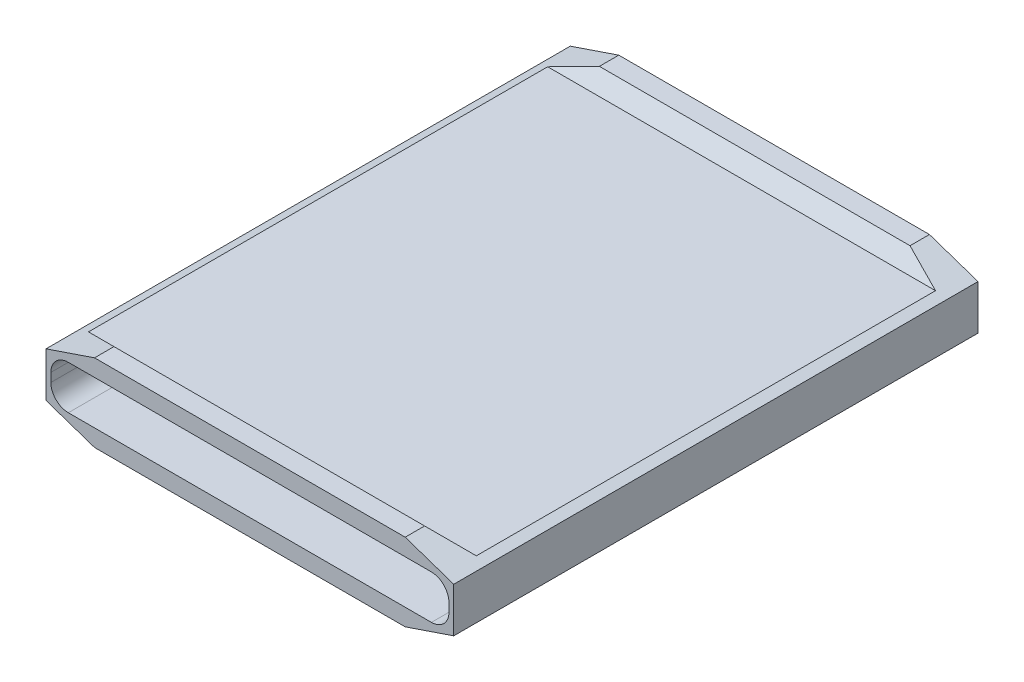
SolidWorks part; units mm, degrees
ref_plane "Front Plane" through (0, 0, 0) normal (0, 0, 1) x (1, 0, 0)
ref_plane "Top Plane" through (0, 0, 0) normal (0, 1, 0) x (1, 0, 0)
ref_plane "Right Plane" through (0, 0, 0) normal (1, 0, 0) x (0, 0, -1)
sketch "Sketch1" plane through (0, 0, 0) normal (0, 0, 1) x (1, 0, 0)
  line L0 (-21, 4) -> (21, 4)
  line L1 (-21, 4) -> (-21, -4)
  line L2 (21, 4) -> (21, -4)
  line L3 (-21, -4) -> (21, -4)
  line L4 (-21, 4) -> (21, -4) construction
  line L5 (21, 4) -> (-21, -4) construction
  line L6 (-20.5, 2.25) -> (20.5, 2.25)
  line L7 (-20.5, 2.25) -> (-20.5, -2.25)
  line L8 (20.5, 2.25) -> (20.5, -2.25)
  line L9 (-20.5, -2.25) -> (20.5, -2.25)
  line L10 (-20.5, 2.25) -> (20.5, -2.25) construction
  line L11 (20.5, 2.25) -> (-20.5, -2.25) construction
  point P1 (0, 0)
  point P2 (0, 0)
  dimension "D1" = 4.5
  dimension "D2" = 41
  dimension "D3" = 42
  dimension "D4" = 8
extrude "Boss-Extrude1" add sketch "Sketch1" along normal blind 54
sketch "Sketch2" plane through (0, 0, 54) normal (0, 0, 1) x (1, 0, 0)
  line L0 (21, 4) -> (-21, 4) construction
  line L1 (-16, 4) -> (-21, 2.3022)
  line L2 (-21, 4) -> (-21, -4) construction
  line L3 (-21, 2.3022) -> (-21, 4)
  line L4 (-21, 4) -> (-16, 4)
  circle A0 centre (-20.5, 3) radius 0.5 construction
  dimension "D1" = 1
  dimension "D2" = 1
  dimension "D3" = 5
extrude "Cut-Extrude1" cut sketch "Sketch2" against normal up to next
mirror "Mirror1" about plane through (0, 0, 0) normal (0, 1, 0) of "Cut-Extrude1"
mirror "Mirror2" about plane through (0, 0, 0) normal (1, 0, 0) of "Mirror1"
fillet "Fillet1" radius 1.8 4 edges at (20.5, 2.25, 27) (20.5, -2.25, 27) (-20.5, -2.25, 27) (-20.5, 2.25, 27)
sketch "Sketch3" plane through (0, 0, 54) normal (0, 0, 1) x (1, 0, 0)
  line L0 (-18.7, -2.25) -> (18.7, -2.25) construction
  line L1 (21, 2.65) -> (-21, 2.65)
  line L2 (21, 2.65) -> (21, -2.65)
  line L3 (21, -2.65) -> (-21, -2.65)
  line L4 (-21, 2.65) -> (-21, -2.65)
  line L5 (21, 2.65) -> (-21, -2.65) construction
  line L6 (21, -2.65) -> (-21, 2.65) construction
  line L7 (-21, 2.3022) -> (-21, -2.3022) construction
  point P0 (0, 0)
  dimension "D1" = 0.4
extrude "Cut-Extrude2" cut sketch "Sketch3" against normal offset from surface (50 mm away) 2 from offset 2 flip side to cut up to face at (0, 0, 0) offset against normal yes
chamfer "Chamfer1" distance 1.35 angle 45 4 edges at (0, -2.65, 2) (0, -2.65, 52) (0, 2.65, 52) (0, 2.65, 2)
